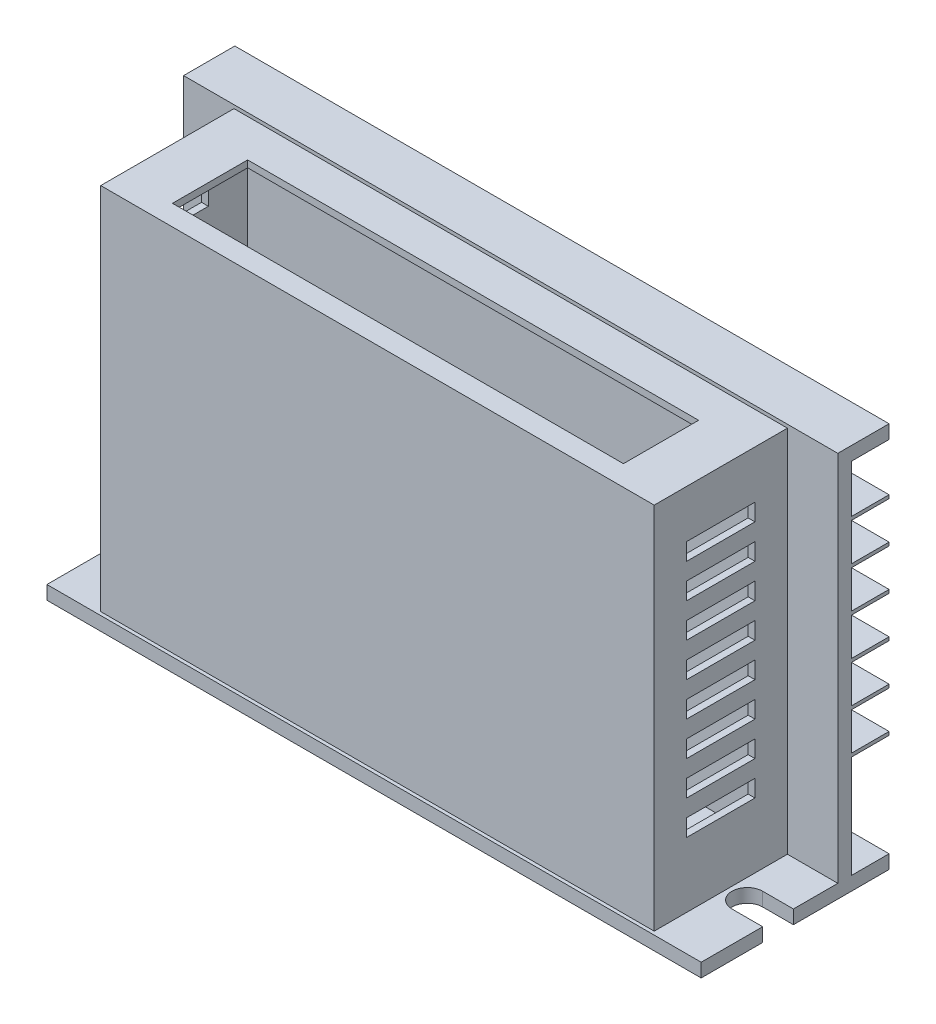
SolidWorks part; units mm, degrees
ref_plane "Front Plane" through (0, 0, 0) normal (0, 0, 1) x (1, 0, 0)
ref_plane "Top Plane" through (0, 0, 0) normal (0, 1, 0) x (1, 0, 0)
ref_plane "Right Plane" through (0, 0, 0) normal (1, 0, 0) x (0, 0, -1)
sketch "Sketch1" plane through (0, 0, 0) normal (0, 1, 0) x (1, 0, 0)
  line L0 (0, -13.75) -> (0, 13.75) construction
  line L1 (-47.875, -13.75) -> (47.875, -13.75)
  line L2 (-47.875, -13.75) -> (-47.875, 13.75)
  line L3 (-47.875, 13.75) -> (47.875, 13.75)
  line L4 (47.875, -13.75) -> (47.875, 13.75)
  line L5 (-47.875, -13.75) -> (47.875, 13.75) construction
  line L6 (-47.875, 13.75) -> (47.875, -13.75) construction
  line L7 (-47.875, -4.75) -> (-43.375, -4.75)
  line L8 (-47.875, -4.75) -> (-47.875, -0.25)
  line L9 (-47.875, -0.25) -> (-43.375, -0.25)
  line L11 (47.875, -4.75) -> (43.375, -4.75)
  line L12 (47.875, -0.25) -> (43.375, -0.25)
  arc A0 (-43.375, -4.75) -> (-43.375, -0.25) centre (-43.375, -2.5) ccw
  arc A1 (43.375, -4.75) -> (43.375, -0.25) centre (43.375, -2.5) cw
  point P0 (0, 0)
  dimension "D5" = 2.25
  dimension "D1" = 27.5
  dimension "D2" = 95.75
  dimension "D3" = 14
  dimension "D4" = 9
  dimension "D6" = 4.5
extrude "Boss-Extrude1" add sketch "Sketch1" along normal blind 2 contours L11 A1 L12 L4 L3 L2 L9 A0 L7 L1 region at (0, 0, -0.0547)
sketch "Sketch2" plane through (-47.875, 0, 0) normal (-1, 0, 0) x (0, 0, 1)
  line L1 (-13.75, 0) -> (-6.25, 0)
  line L2 (-13.75, 0) -> (-13.75, 2)
  line L3 (-13.75, 56.5) -> (-6.25, 56.5)
  line L4 (-6.25, 0) -> (-6.25, 56.5)
  line L7 (-13.75, 54.5) -> (-13.75, 56.5)
  line L39 (-13.75, 54.5) -> (-8.25, 54.5)
  line L40 (-8.25, 54.5) -> (-8.25, 47.5)
  line L41 (0.25, 2) -> (-13.75, 2) construction
  line L42 (-8.25, 2) -> (-13.75, 2)
  line L43 (-8.25, 17.5) -> (-13.75, 17.5)
  line L44 (-8.25, 11.5) -> (-13.75, 11.5)
  line L45 (-8.25, 11.5) -> (-8.25, 11)
  line L46 (-8.25, 11) -> (-13.75, 11)
  line L58 (-13.75, 11.5) -> (-13.75, 11)
  line L59 (-13.75, 17.5) -> (-13.75, 17)
  line L60 (-8.25, 17) -> (-13.75, 17)
  line L61 (-8.25, 23.5) -> (-13.75, 23.5)
  line L62 (-13.75, 23.5) -> (-13.75, 23)
  line L63 (-8.25, 23) -> (-13.75, 23)
  line L64 (-8.25, 29.5) -> (-13.75, 29.5)
  line L65 (-13.75, 29.5) -> (-13.75, 29)
  line L66 (-8.25, 29) -> (-13.75, 29)
  line L67 (-8.25, 35.5) -> (-13.75, 35.5)
  line L68 (-13.75, 35.5) -> (-13.75, 35)
  line L69 (-8.25, 35) -> (-13.75, 35)
  line L70 (-8.25, 41.5) -> (-13.75, 41.5)
  line L71 (-13.75, 41.5) -> (-13.75, 41)
  line L72 (-8.25, 41) -> (-13.75, 41)
  line L73 (-8.25, 47.5) -> (-13.75, 47.5)
  line L74 (-13.75, 47.5) -> (-13.75, 47)
  line L75 (-8.25, 47) -> (-13.75, 47)
  line L76 (-8.25, 11.5) -> (-8.25, 17) construction
  line L77 (-8.25, 17) -> (-8.25, 2)
  line L78 (-8.25, 23) -> (-8.25, 17.5)
  line L79 (-8.25, 29) -> (-8.25, 23.5)
  line L80 (-8.25, 35) -> (-8.25, 29.5)
  line L81 (-8.25, 41) -> (-8.25, 35.5)
  line L82 (-8.25, 47) -> (-8.25, 41.5)
  dimension "D1" = 7.5
  dimension "D2" = 56.5
  dimension "D4" = 2
  dimension "D5" = 0.5
  dimension "D7" = 6
  dimension "D3" = 2
  dimension "D6" = 9
extrude "Boss-Extrude4" add sketch "Sketch2" against normal up to surface (95.75 mm away) contours L4 L3 L7 L39 L40 L73 L74 L75 L82 L70 L71 L72 L81 L67 L68 L69 L80 L64 L65 L66 L79 L61 L62 L63 L78 L43 L59 L60 L77 L42 L2 L1 up to face at (47.875, 1, -6.75)
sketch "Sketch3" plane through (0, 2, 0) normal (0, 1, 0) x (1, 0, 0)
  line L1 (-40.5, -13.25) -> (40.5, -13.25)
  line L2 (-40.5, -13.25) -> (-40.5, 6.25)
  line L3 (-40.5, 6.25) -> (40.5, 6.25)
  line L4 (40.5, -13.25) -> (40.5, 6.25)
  line L5 (47.875, 6.25) -> (-47.875, 6.25) construction
  line L6 (0, 6.25) -> (0, -13.25) construction
  line L7 (47.875, -0.25) -> (47.875, 6.25) construction
  line L8 (-47.875, -0.25) -> (-47.875, 6.25) construction
  line L9 (-47.875, -13.75) -> (47.875, -13.75) construction
  dimension "D1" = 81
  dimension "D2" = 0.5
extrude "Boss-Extrude5" add sketch "Sketch3" along normal offset from surface (54 mm away) 0.5 contours L2 L3 L4 L1 up to face at (0, 56.5, -10)
sketch "Sketch4" plane through (40.5, 0, 0) normal (1, 0, 0) x (0, 0, -1)
  line L0 (6.25, 56) -> (-13.25, 56) construction
  line L1 (-8.5, 46.5) -> (1.5, 46.5)
  line L2 (-8.5, 46.5) -> (-8.5, 49)
  line L3 (-8.5, 49) -> (1.5, 49)
  line L4 (1.5, 46.5) -> (1.5, 49)
  line L5 (-13.25, 56) -> (-13.25, 2) construction
  line L7 (-8.5, 41.5) -> (-8.5, 44)
  line L8 (-8.5, 41.5) -> (1.5, 41.5)
  line L9 (1.5, 41.5) -> (1.5, 44)
  line L10 (-8.5, 44) -> (1.5, 44)
  line L11 (-8.5, 36.5) -> (-8.5, 39)
  line L12 (-8.5, 36.5) -> (1.5, 36.5)
  line L13 (1.5, 36.5) -> (1.5, 39)
  line L14 (-8.5, 39) -> (1.5, 39)
  line L15 (-8.5, 31.5) -> (-8.5, 34)
  line L16 (-8.5, 31.5) -> (1.5, 31.5)
  line L17 (1.5, 31.5) -> (1.5, 34)
  line L18 (-8.5, 34) -> (1.5, 34)
  line L19 (-8.5, 26.5) -> (-8.5, 29)
  line L20 (-8.5, 26.5) -> (1.5, 26.5)
  line L21 (1.5, 26.5) -> (1.5, 29)
  line L22 (-8.5, 29) -> (1.5, 29)
  line L23 (-8.5, 21.5) -> (-8.5, 24)
  line L24 (-8.5, 21.5) -> (1.5, 21.5)
  line L25 (1.5, 21.5) -> (1.5, 24)
  line L26 (-8.5, 24) -> (1.5, 24)
  line L27 (-8.5, 16.5) -> (-8.5, 19)
  line L28 (-8.5, 16.5) -> (1.5, 16.5)
  line L29 (1.5, 16.5) -> (1.5, 19)
  line L30 (-8.5, 19) -> (1.5, 19)
  line L31 (-8.5, 11.5) -> (-8.5, 14)
  line L32 (-8.5, 11.5) -> (1.5, 11.5)
  line L33 (1.5, 11.5) -> (1.5, 14)
  line L34 (-8.5, 14) -> (1.5, 14)
  line L35 (-8.5, 46.5) -> (-8.5, 41.5) construction
  dimension "D1" = 10
  dimension "D2" = 2.5
  dimension "D3" = 7
  dimension "D4" = 4.75
  dimension "D5" = 5
extrude "Cut-Extrude1" cut sketch "Sketch4" against normal blind 1
shell "Shell1" thickness 1 removed face at (39.5, 12.75, 3.5) removed face at (39.5, 17.75, 3.5) removed face at (39.5, 22.75, 3.5) removed face at (39.5, 27.75, 3.5) removed face at (39.5, 32.75, 3.5) removed face at (39.5, 37.75, 3.5) removed face at (39.5, 42.75, 3.5) removed face at (39.5, 47.75, 3.5)
extrude "Cut-Extrude2" cut sketch "Sketch4<2>" against normal through all contours L1 L4 L3 L2 | L32 L33 L34 L31 | L28 L29 L30 L27
sketch "Sketch4<2>" plane through (40.5, 0, 0) normal (1, 0, 0) x (0, 0, -1) same geometry as "Sketch4"
sketch "Sketch5" plane through (-40.5, 0, 0) normal (-1, 0, 0) x (0, 0, 1)
  line L0 (13.25, 56) -> (13.25, 2) construction
  line L1 (0, 39.5) -> (10, 39.5)
  line L2 (0, 39.5) -> (0, 21)
  line L3 (0, 21) -> (10, 21)
  line L4 (10, 39.5) -> (10, 21)
  line L5 (-1.5, 19) -> (8.5, 19) construction
  dimension "D1" = 10
  dimension "D2" = 3.25
  dimension "D3" = 18.5
  dimension "D4" = 2
extrude "Cut-Extrude3" cut sketch "Sketch5" against normal up to next contours L4 L3 L2 L1
sketch "Sketch6" plane through (0, 56, 0) normal (0, 1, 0) x (1, 0, 0)
  line L0 (40.5, -13.25) -> (-40.5, -13.25) construction
  line L1 (33, 0.75) -> (-33, 0.75)
  line L2 (33, 0.75) -> (33, -10.25)
  line L3 (33, -10.25) -> (-33, -10.25)
  line L4 (-33, 0.75) -> (-33, -10.25)
  line L5 (0, -10.25) -> (0, 0.75) construction
  line L6 (40.5, 6.25) -> (40.5, -13.25) construction
  line L7 (-40.5, 6.25) -> (-40.5, -13.25) construction
  dimension "D1" = 11
  dimension "D2" = 3
  dimension "D3" = 66
extrude "Cut-Extrude4" cut sketch "Sketch6" against normal up to surface (1 mm away) up to face at (0, 55, 2.5)
